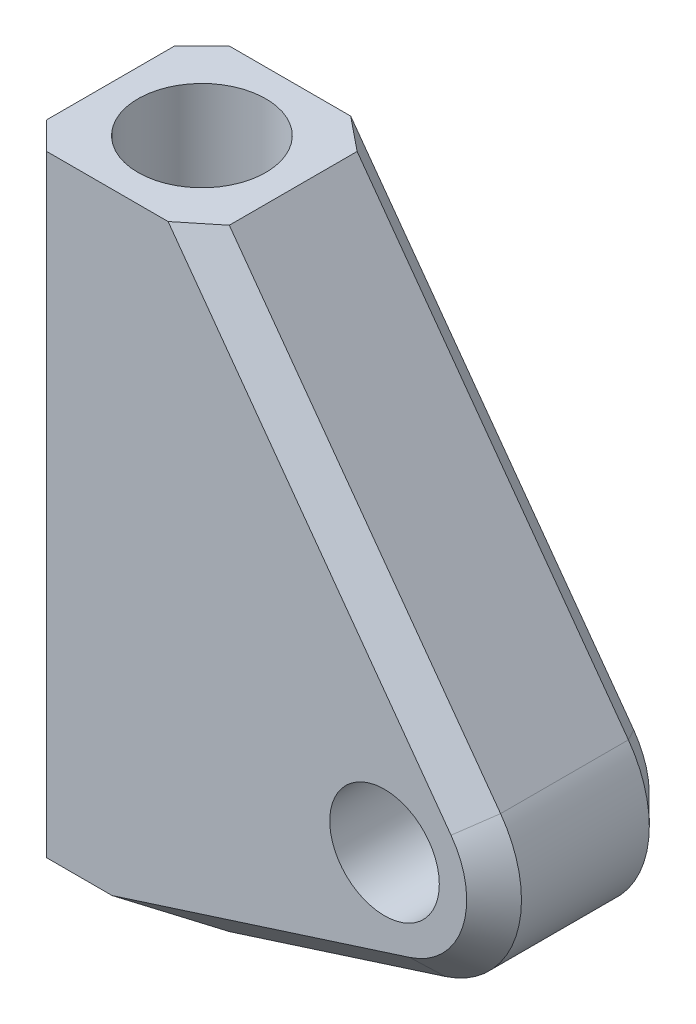
SolidWorks part; units mm, degrees
material "PUR"
ref_plane "Płaszczyzna przednia" through (0, 0, 0) normal (0, 0, 1) x (1, 0, 0)
ref_plane "Płaszczyzna górna" through (0, 0, 0) normal (0, 1, 0) x (1, 0, 0)
ref_plane "Płaszczyzna prawa" through (0, 0, 0) normal (1, 0, 0) x (0, 0, -1)
sketch "Szkic1" plane through (0, 0, 0) normal (0, 0, 1) x (1, 0, 0)
  line L0 (0, 0) -> (0, 67)
  line L1 (0, 67) -> (20, 67)
  line L2 (0, 0) -> (20, 0)
  line L3 (20, 67) -> (49.7129, 26.047)
  line L4 (20, 0) -> (43.6576, 7.571)
  circle A0 centre (40, 19) radius 6
  arc A1 (43.6576, 7.571) -> (49.7129, 26.047) centre (40, 19) ccw
  dimension "D3" = 12
  dimension "D6" = 24
  dimension "D1" = 67
  dimension "D2" = 20
  dimension "D4" = 40
  dimension "D5" = 19
extrude "Dodanie-wyciągnięcie1" add sketch "Szkic1" along normal blind 20
sketch "Szkic2" plane through (0, 67, 0) normal (0, 1, 0) x (1, 0, 0)
  line L0 (0, -20) -> (0, 0) construction
  line L1 (20, -20) -> (0, -20) construction
  circle A0 centre (10, -10) radius 7
  point P6 (-13.6239, -2.8016)
  dimension "D1" = 14
  dimension "D2" = 10
  dimension "D3" = 10
extrude "Wytnij-wyciągnięcie1" cut sketch "Szkic2" against normal through all
chamfer "Sfazowanie1" distance 3 angle 45 8 edges at (0, 33.5, 0) (0, 33.5, 20) (31.8288, 3.7855, 20) (51.4032, 15.2627, 20) (34.8564, 46.5235, 20) (31.8288, 3.7855, 0) (51.4032, 15.2627, 0) (34.8564, 46.5235, 0)
